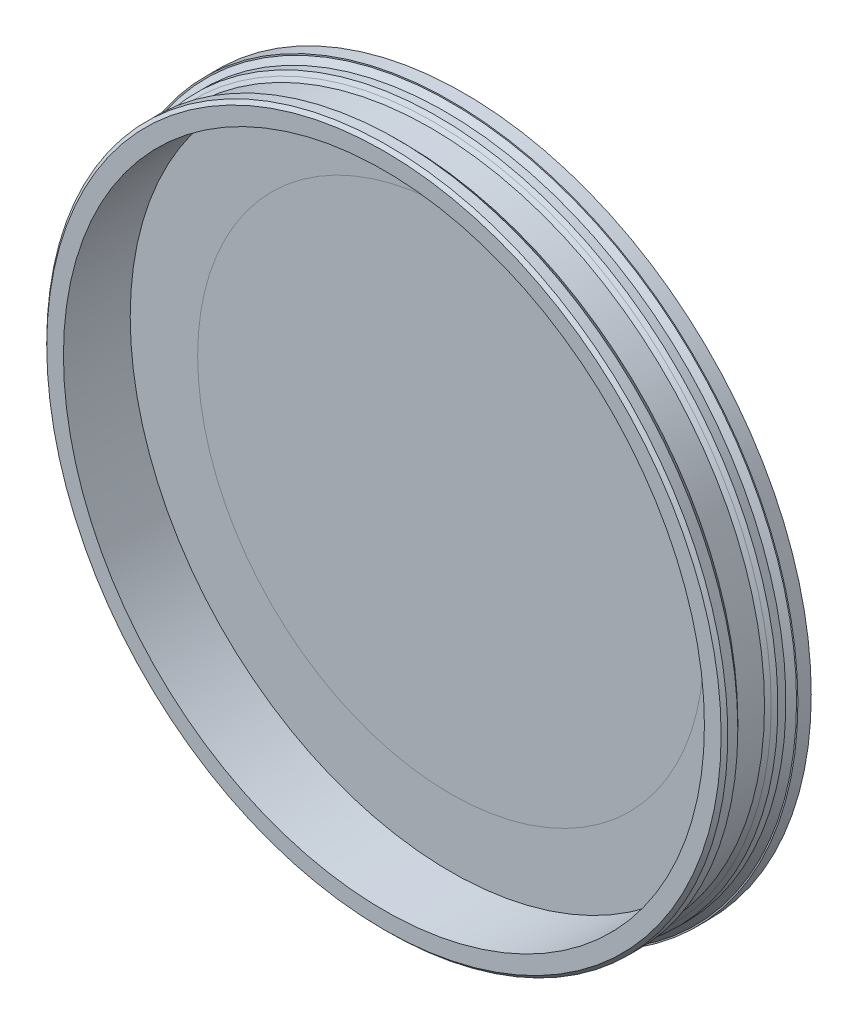
SolidWorks part; units mm, degrees
ref_plane "Front Plane" through (0, 0, 0) normal (0, 0, 1) x (1, 0, 0)
ref_plane "Top Plane" through (0, 0, 0) normal (0, 1, 0) x (1, 0, 0)
ref_plane "Right Plane" through (0, 0, 0) normal (1, 0, 0) x (0, 0, -1)
sketch "Sketch1" plane through (0, 0, 0) normal (0, 1, 0) x (1, 0, 0)
  line L0 (0, 73.9814) -> (0, -55.3241) construction
  line L1 (-91.4726, 0) -> (90.4361, 0) construction
  line L2 (37.9, 0) -> (37.9, -8.7)
  line L3 (48, -18.7) -> (51, -18.7)
  line L4 (51, -18.7) -> (51, -16.2)
  line L5 (51, -16.2) -> (50, -16.2)
  line L6 (50, -16.2) -> (50, -11.2)
  line L7 (50, -11.2) -> (51, -11.2)
  line L8 (51, -11.2) -> (51, -8.7)
  line L9 (51, -8.7) -> (52, -8.7)
  line L10 (52, -8.7) -> (52, -6.7)
  line L11 (52, -6.7) -> (39.9, -6.7)
  line L12 (39.9, -6.7) -> (39.9, 0)
  line L13 (39.9, 0) -> (37.9, 0)
  line L14 (37.9, -8.7) -> (48, -8.7)
  line L15 (48, -8.7) -> (48, -18.7)
  dimension "D1" = 52
  dimension "D2" = 39.9
  dimension "D3" = 51
  dimension "D4" = 6.7
  dimension "D5" = 2
  dimension "D6" = 2
  dimension "D7" = 10
  dimension "D8" = 5
  dimension "D9" = 2.5
  dimension "D10" = 1
  dimension "D11" = 51
  dimension "D12" = 3
revolve "Revolve1" add sketch "Sketch1" angle 360 about L0
chamfer "Chamfer1" distance 0.5 angle 45 6 edges at (-51, 0, 11.2) (-50, 0, 11.2) (-50, 0, 16.2) (-51, 0, 16.2) (-39.9, 0, 0) (-51, 0, 18.7)
sketch "Sketch2" plane through (0, 0, 8.7) normal (0, 0, 1) x (1, 0, 0)
  line L0 (0, 99.1772) -> (0, -96.216) construction
  line L1 (-93.7434, 0) -> (96.5768, 0) construction
  line L2 (-78.2888, 55.25) -> (80.948, 55.25) construction
  line L3 (9.798, 59.25) -> (33.218, 59.25)
  line L4 (-9.798, 59.25) -> (-33.218, 59.25)
  line L12 (46.413, -38.1103) -> (34.703, -58.3926)
  line L13 (56.211, -21.1397) -> (67.921, -0.8574)
  line L14 (85.89, -49.5886) -> (-83.3255, 48.108) construction
  line L15 (86.9923, 40.1751) -> (7.3739, -97.7281) construction
  line L16 (-56.211, -21.1397) -> (-67.921, -0.8574)
  line L17 (-46.413, -38.1103) -> (-34.703, -58.3926)
  line L18 (-85.89, -49.5886) -> (83.3255, 48.108) construction
  line L19 (-8.7035, -95.4251) -> (-88.3219, 42.4781) construction
  line L20 (-33.218, 59.25) -> (-67.921, -0.8574)
  line L21 (-34.703, -58.3926) -> (34.703, -58.3926)
  line L22 (67.921, -0.8574) -> (33.218, 59.25)
  arc A0 (-9.798, 59.25) -> (9.798, 59.25) centre (0, 69.25) ccw
  arc A3 (56.211, -21.1397) -> (46.413, -38.1103) centre (59.9723, -34.625) ccw
  circle A5 centre (0, 0) radius 51 construction
  circle A6 centre (0, 0) radius 51
  arc A7 (-46.413, -38.1103) -> (-56.211, -21.1397) centre (-59.9723, -34.625) ccw
  point P25 (0, 0)
  point P37 (0, 0)
  dimension "D2" = 28
  dimension "D5" = 3
  dimension "D1" = 55.25
  dimension "D3" = 4
  dimension "D4" = 23.42
chamfer "Chamfer2" distance 0.8 angle 45 1 edges at (-51, 0, 8.7)
sketch "Sketch3" plane through (0, 0, 0) normal (0, 1, 0) x (1, 0, 0)
  line L0 (-56.8245, -6.7) -> (62.1624, -6.7) construction
  line L2 (-48.6609, 19.4392) -> (55.8999, 19.4392)
  line L3 (-48.6609, 19.4392) -> (-48.6609, -6.7)
  line L4 (-48.6609, -6.7) -> (55.8999, -6.7)
  line L5 (55.8999, 19.4392) -> (55.8999, -6.7)
extrude "Cut-Extrude1" cut sketch "Sketch3" against normal through all both and the other way through all
sketch "Sketch4" plane through (0, 0, 6.7) normal (0, 0, -1) x (-1, 0, 0)
  circle A0 centre (0, 0) radius 37.9 construction
  circle A1 centre (0, 0) radius 37.9
extrude "Boss-Extrude1" add sketch "Sketch4" against normal blind 2 separate body
